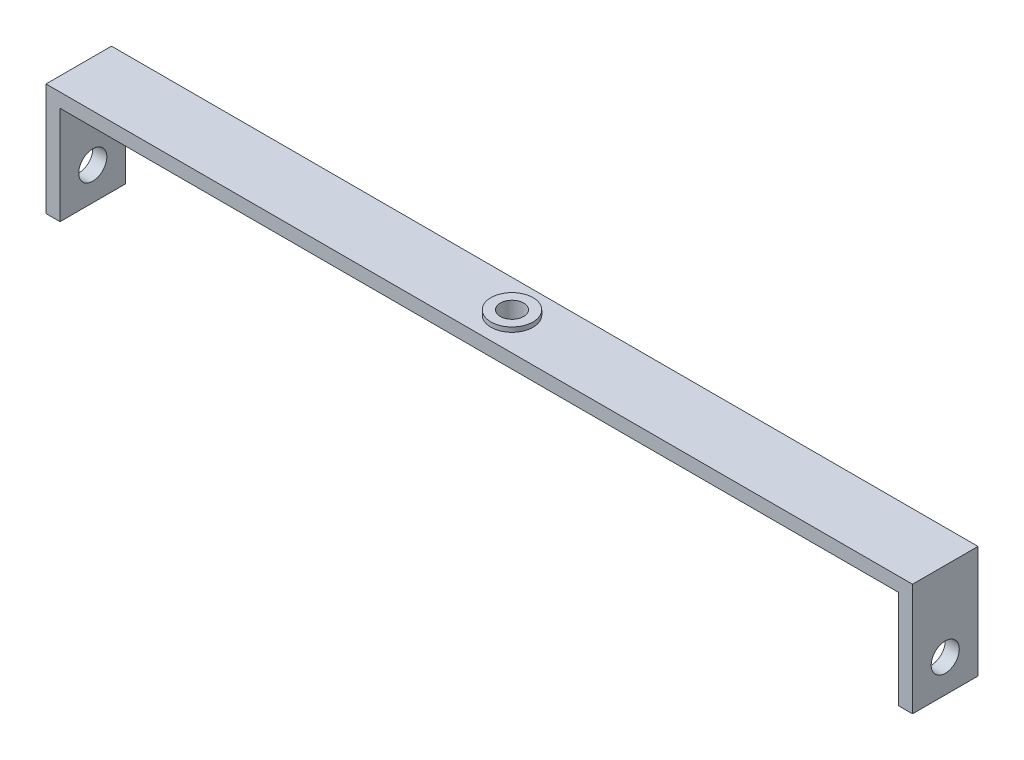
SolidWorks part; units mm, degrees
ref_plane "Front Plane" through (0, 0, 0) normal (0, 0, 1) x (1, 0, 0)
ref_plane "Top Plane" through (0, 0, 0) normal (0, 1, 0) x (1, 0, 0)
ref_plane "Right Plane" through (0, 0, 0) normal (1, 0, 0) x (0, 0, -1)
sketch "Sketch1" plane through (0, 0, 0) normal (0, 0, 1) x (1, 0, 0)
  line L0 (-46.3, 0) -> (46.3, 0)
  line L1 (46.3, 0) -> (46.3, -12)
  line L2 (-46.3, 0) -> (-46.3, -12)
  line L3 (-44.8, -1.5) -> (-44.8, -12)
  line L4 (-44.8, -1.5) -> (44.8, -1.5)
  line L5 (44.8, -1.5) -> (44.8, -12)
  line L6 (-46.3, -12) -> (-44.8, -12)
  line L7 (44.8, -12) -> (46.3, -12)
  point P4 (0, 0)
  dimension "D1" = 92.6
  dimension "D2" = 12
  dimension "D3" = 1.5
extrude "Boss-Extrude1" add sketch "Sketch1" along normal blind 3.5 and the other way blind 3.5
sketch "Sketch2" plane through (0, 0, 0) normal (0, 1, 0) x (1, 0, 0)
  circle A0 centre (0, 0) radius 1.25
  dimension "D1" = 2.5
extrude "Cut-Extrude1" cut sketch "Sketch2" against normal blind 3.5
sketch "Sketch3" plane through (0, 0, 0) normal (0, 1, 0) x (1, 0, 0)
  circle A1 centre (0, 0) radius 1.25 construction
  circle A2 centre (0, 0) radius 2.25
  circle A3 centre (0, 0) radius 2.25
  circle A4 centre (0, 0) radius 1.25
  dimension "D1" = 1
extrude "Boss-Extrude2" add sketch "Sketch3" along normal blind 0.5
sketch "Sketch4" plane through (0, 0, 0) normal (1, 0, 0) x (0, 0, -1)
  line L0 (0, 0) -> (0, -8.5) construction
  line L1 (3.5, 0) -> (-3.5, 0) construction
  circle A0 centre (0, -8.5) radius 1.5
  dimension "D2" = 3
  dimension "D1" = 8.5
extrude "Cut-Extrude2" cut sketch "Sketch4" against normal up to surface and the other way up to surface up to face at (-46.3, -6, 0) other way up to face at (46.3, -6, 0)
